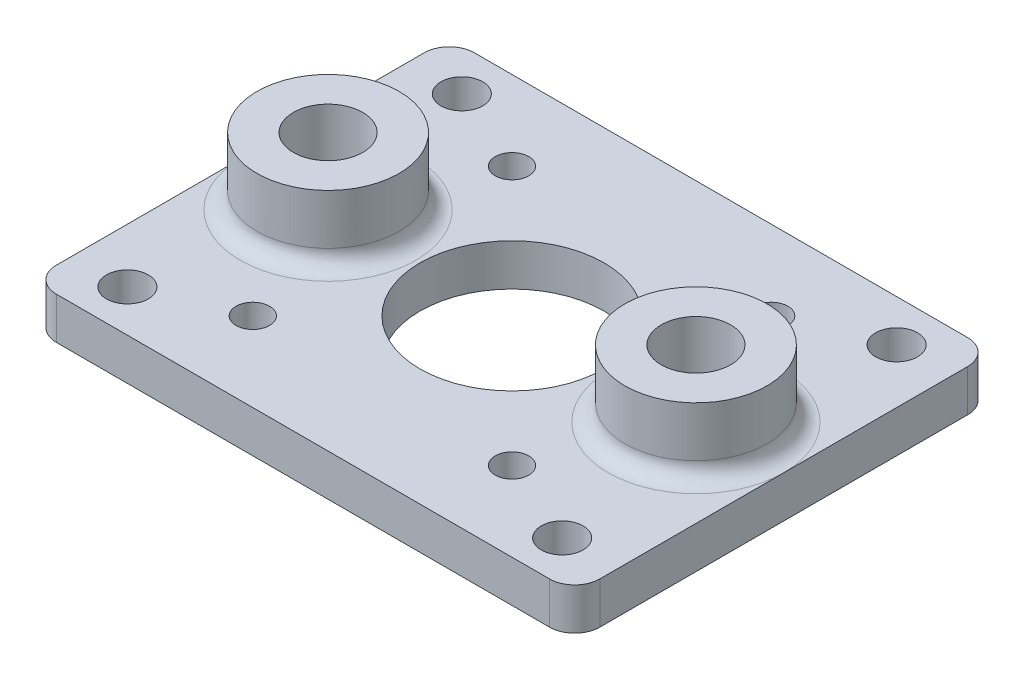
SolidWorks part; units mm, degrees
ref_plane "Front Plane" through (0, 0, 0) normal (0, 0, 1) x (1, 0, 0)
ref_plane "Top Plane" through (0, 0, 0) normal (0, 1, 0) x (1, 0, 0)
ref_plane "Right Plane" through (0, 0, 0) normal (1, 0, 0) x (0, 0, -1)
sketch "Sketch1" plane through (0, 0, 0) normal (0, 1, 0) x (1, 0, 0)
  line L1 (-32.5, 25) -> (32.5, 25)
  line L2 (-32.5, 25) -> (-32.5, -25)
  line L3 (-32.5, -25) -> (32.5, -25)
  line L4 (32.5, 25) -> (32.5, -25)
  circle A0 centre (0, 0) radius 11
  circle A1 centre (15.5, 15.5) radius 2
  circle A2 centre (-15.5, 15.5) radius 2
  circle A3 centre (15.5, -15.5) radius 2
  circle A4 centre (-15.5, -15.5) radius 2
  circle A5 centre (26, 20) radius 2.5
  circle A6 centre (-26, 20) radius 2.5
  circle A7 centre (-26, -20) radius 2.5
  circle A8 centre (26, -20) radius 2.5
  point P0 (0, 0)
  dimension "D3" = 31
  dimension "D5" = 52
  dimension "D1" = 65
  dimension "D2" = 50
  dimension "D4" = 31
extrude "Boss-Extrude1" add sketch "Sketch1" along normal blind 5
sketch "Sketch2" plane through (0, 5, 0) normal (0, 1, 0) x (1, 0, 0)
  line L0 (0, 0) -> (22, 0) construction
  line L1 (0, 20.574) -> (0, -23.3725) construction
  circle A2 centre (22, 0) radius 4.15
  circle A3 centre (22, 0) radius 8.5
  circle A4 centre (-22, 0) radius 8.5
  circle A5 centre (-22, 0) radius 4.15
  dimension "D1" = 22
  dimension "D2" = 8.3
extrude "Boss-Extrude2" add sketch "Sketch2" along normal blind 8
fillet "Fillet1" radius 3 4 edges at (-32.5, 2.5, -25) (-32.5, 2.5, 25) (32.5, 2.5, 25) (32.5, 2.5, -25)
sketch "Sketch3" plane through (0, 5, 0) normal (0, 1, 0) x (1, 0, 0)
  circle A0 centre (-22, 0) radius 4.15
  circle A1 centre (22, 0) radius 4.15
extrude "Cut-Extrude1" cut sketch "Sketch3" against normal blind 8
fillet "Fillet2" radius 2 2 edges at (22, 5, 8.5) (-22, 5, -8.5)
